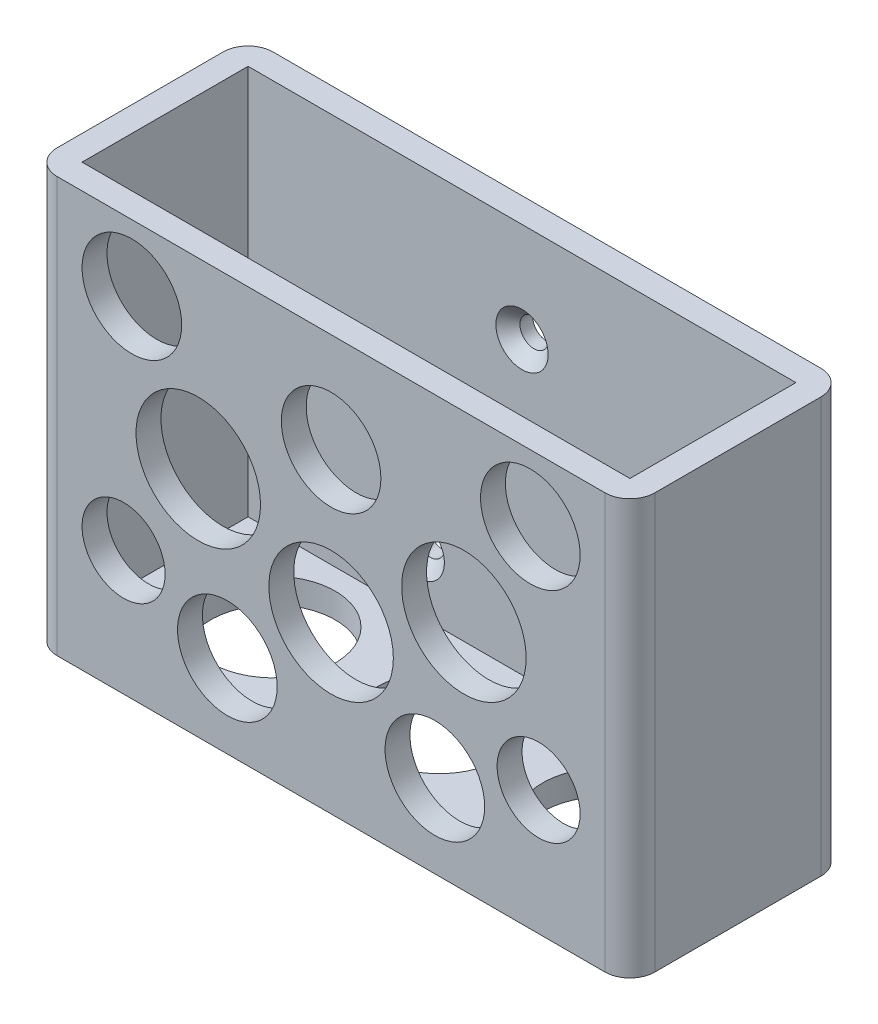
SolidWorks part; units mm, degrees
ref_plane "Front Plane" through (0, 0, 0) normal (0, 0, 1) x (1, 0, 0)
ref_plane "Top Plane" through (0, 0, 0) normal (0, 1, 0) x (1, 0, 0)
ref_plane "Right Plane" through (0, 0, 0) normal (1, 0, 0) x (0, 0, -1)
sketch "Sketch1" plane through (0, 0, 0) normal (0, 1, 0) x (1, 0, 0)
  line L1 (36, 13) -> (-36, 13)
  line L2 (36, 13) -> (36, -13)
  line L3 (36, -13) -> (-36, -13)
  line L4 (-36, 13) -> (-36, -13)
  line L5 (36, 13) -> (-36, -13) construction
  line L6 (36, -13) -> (-36, 13) construction
  point P0 (0, 0)
  dimension "D1" = 72
  dimension "D2" = 26
extrude "Boss-Extrude1" add sketch "Sketch1" along normal blind 50
fillet "Fillet1" radius 3 4 edges at (-36, 25, -13) (36, 25, -13) (36, 25, 13) (-36, 25, 13)
shell "Shell1" thickness 3 removed face at (0, 50, 0)
sketch "Sketch2" plane through (0, 3, 0) normal (0, 1, 0) x (1, 0, 0)
  line L0 (0, 0) -> (50000, 0) construction
  line L1 (0, 5.9967) -> (0, 50005.9967) construction
  circle A0 centre (0, 0) radius 7.5
  circle A1 centre (-20, 0) radius 7.5
  circle A2 centre (20, 0) radius 7.5
  dimension "D1" = 15
  dimension "D2" = 40
extrude "Cut-Extrude1" cut sketch "Sketch2" against normal through all
hole_wizard "CSK for M3 Countersunk Flat Head Screw1" positions "Sketch5" profile "Sketch4" countersink size "M3" standard "ISO" end condition through all
sketch "Sketch5" plane through (0, 0, -10) normal (0, 0, 1) x (1, 0, 0)
  line L0 (0, 0) -> (0, 50000) construction
  line L1 (33, 50) -> (-33, 50) construction
  line L2 (33, 0) -> (-33, 0) construction
  point P0 (0, 38)
  point P2 (-12.5, 10)
  point P4 (12.5, 10)
  dimension "D1" = 12
  dimension "D2" = 10
  dimension "D3" = 25
sketch "Sketch4" plane through (0, 38, -10) normal (1, 0, 0) x (0, -1, 0)
  line L0 (0, 0) -> (0, 3)
  line L1 (0, 3) -> (1.7, 3)
  line L2 (1.7, 3) -> (1.7, 1.45)
  line L3 (1.7, 1.45) -> (3.15, 0)
  line L5 (3.15, 0) -> (0, 0)
  line L6 (-1.7, 1.45) -> (-3.15, 0) construction
  line L11 (0, -6.35) -> (0, 107.95) construction
  dimension "Thru Hole Dia." = 3.4
  dimension "Thru Hole Depth" = 3
  dimension "Near C'Sink Dia." = 6.3
  dimension "Near C'Sink Angle" = 90
sketch "Sketch6" plane through (0, 0, 13) normal (0, 0, 1) x (1, 0, 0)
  line L0 (-12.784, 42) -> (49987.216, 42) construction
  line L1 (-2.3978, 15) -> (49997.6022, 15) construction
  line L2 (0, 0) -> (0, 50000) construction
  line L3 (-33, 0) -> (33, 0) construction
  line L4 (-8.6379, 28) -> (49991.3621, 28) construction
  circle A0 centre (0, 38) radius 6
  circle A1 centre (-12.5, 10) radius 6
  circle A2 centre (12.5, 10) radius 6
  circle A3 centre (0, 20) radius 7.5
  circle A4 centre (24, 42) radius 6
  circle A5 centre (16, 28) radius 7.5
  circle A6 centre (-16, 28) radius 7.5
  circle A7 centre (-24, 42) radius 6
  circle A8 centre (25, 15) radius 5
  circle A9 centre (-25, 15) radius 5
  point P31 (0, 0)
  dimension "D1" = 12
  dimension "D2" = 15
  dimension "D3" = 12
  dimension "D4" = 10
  dimension "D8" = 15
  dimension "D5" = 48
  dimension "D6" = 32
  dimension "D7" = 50
  dimension "D9" = 15
  dimension "D10" = 28
  dimension "D11" = 42
  dimension "D12" = 20
extrude "Cut-Extrude2" cut sketch "Sketch6" against normal up to next
